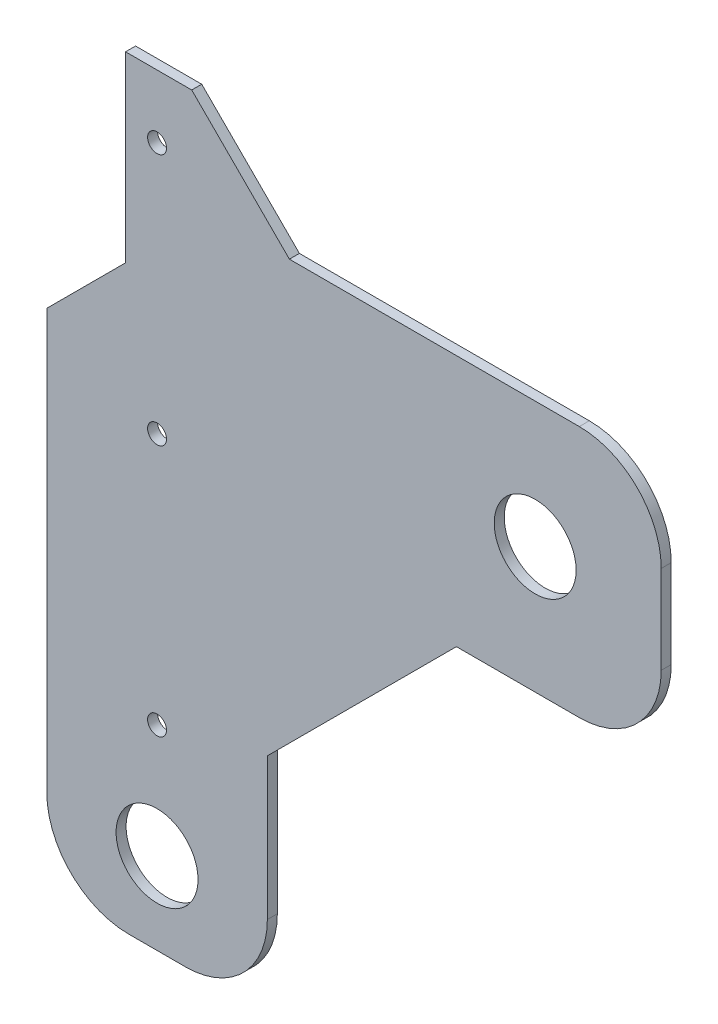
SolidWorks part; units mm, degrees
material "6061 Alloy"
ref_plane "Front Plane" through (0, 0, 0) normal (0, 0, 1) x (1, 0, 0)
ref_plane "Top Plane" through (0, 0, 0) normal (0, 1, 0) x (1, 0, 0)
ref_plane "Right Plane" through (0, 0, 0) normal (1, 0, 0) x (0, 0, -1)
sketch "Sketch1" plane through (0, 0, 0) normal (0, 0, 1) x (1, 0, 0)
  line L0 (0, 0) -> (0, 50)
  line L2 (35, 39.5) -> (35, 0)
  line L6 (0, 0) -> (35, 0) construction
  line L7 (5, 50) -> (5, 0) construction
  line L8 (0, 0) -> (5, 0) construction
  line L9 (5, 45) -> (5, 50) construction
  line L10 (17.5, 50) -> (17.5, -13) construction
  line L11 (0, 0) -> (0, -26)
  line L12 (0, -26) -> (35, -26)
  line L13 (0, 25) -> (5, 25) construction
  line L14 (35, -26) -> (35, 0)
  line L15 (17.5, -13) -> (17.5, 5) construction
  line L16 (17.5, 5) -> (30, 5) construction
  line L17 (77.5, 59.5) -> (17.5, 59.5) construction
  line L18 (17.5, 59.5) -> (17.5, 50) construction
  line L20 (35, 79.5) -> (97.5, 79.5)
  line L21 (97.5, 79.5) -> (97.5, 39.5)
  line L22 (97.5, 39.5) -> (35, 39.5)
  line L23 (77.5, 59.5) -> (77.5, 39.5) construction
  line L24 (77.5, 59.5) -> (77.5, 79.5) construction
  line L25 (77.5, 59.5) -> (97.5, 59.5) construction
  line L26 (35, 39.5) -> (35, 50) construction
  line L27 (35, 50) -> (17.5, 50) construction
  line L28 (17.5, 50) -> (5, 50) construction
  line L29 (5, 50) -> (0, 50) construction
  line L30 (5, 45) -> (30, 45) construction
  line L31 (5, 25) -> (30, 25) construction
  line L32 (5, 5) -> (30, 5) construction
  line L34 (12.5, 95) -> (22.5, 95)
  line L36 (17.5, 59.5) -> (17.5, 95) construction
  line L37 (12.5, 95) -> (12.5, 50)
  line L38 (12.5, 50) -> (0, 50)
  line L39 (35, 79.5) -> (22.5, 79.5)
  line L40 (22.5, 79.5) -> (22.5, 95)
  line L41 (22.5, 85) -> (17.5, 85) construction
  line L42 (17.5, 85) -> (12.5, 85) construction
  circle A0 centre (17.5, -13) radius 6.5
  circle A1 centre (5, 45) radius 1.5 construction
  circle A2 centre (5, 25) radius 1.5 construction
  circle A3 centre (5, 5) radius 1.5 construction
  circle A4 centre (30, 5) radius 1.5 construction
  circle A5 centre (30, 25) radius 1.5 construction
  circle A6 centre (30, 45) radius 1.5 construction
  circle A7 centre (77.5, 59.5) radius 6.5
  circle A8 centre (17.5, 45) radius 1.5
  circle A9 centre (17.5, 25) radius 1.5 construction
  circle A10 centre (17.5, 5) radius 1.5
  circle A12 centre (17.5, 85) radius 1.5
  dimension "D5" = 13
  dimension "D7" = 3
  dimension "D9" = 20
  dimension "D10" = 20
  dimension "D11" = 72.5
  dimension "D16" = 40
  dimension "D2" = 50
  dimension "D3" = 13
  dimension "D4" = 13
  dimension "D6" = 5
  dimension "D8" = 5
  dimension "D12" = 60
  dimension "D13" = 20
  dimension "D14" = 5
  dimension "D15" = 35
  dimension "D17" = 10
  dimension "D18" = 10
extrude "Boss-Extrude1" add sketch "Sketch1" along normal blind 1.5875
fillet "Fillet1" [suppressed] radius 5
fillet "Fillet2" radius 13 4 edges at (35, -26, 0.7937) (0, -26, 0.7937) (97.5, 39.5, 0.7937) (97.5, 79.5, 0.7937)
chamfer "Chamfer1" distance 30 angle 45 1 edges at (35, 39.5, 0.7937)
chamfer "Chamfer2" distance 16 angle 45 2 edges at (22.5, 79.5, 0.7937) (12.5, 50, 0.7937)
